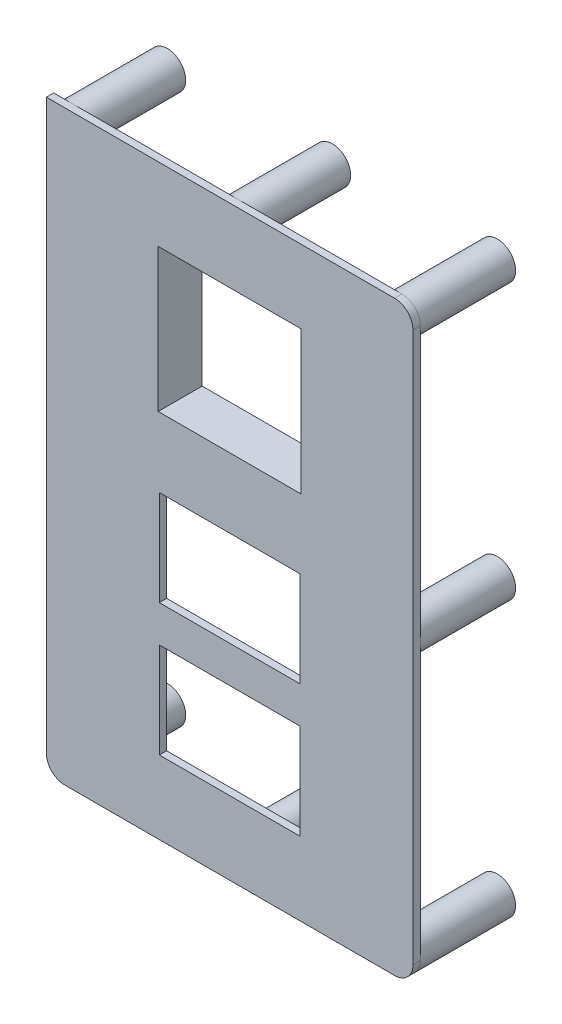
SolidWorks part; units mm, degrees
ref_plane "Front Plane" through (0, 0, 0) normal (1, 0, 0) x (0, 1, 0)
ref_plane "Top Plane" through (0, 0, 0) normal (0, 0, 1) x (0, 1, 0)
ref_plane "Right Plane" through (0, 0, 0) normal (0, 1, 0) x (-1, 0, 0)
sketch "Sketch1" plane through (0, 0, 0) normal (0, 0, 1) x (0, 1, 0)
  line L0 (-40, 0) -> (40, 0) construction
  line L1 (-40, -25) -> (40, -25)
  line L2 (-40, -25) -> (-40, 25)
  line L3 (-40, 25) -> (40, 25)
  line L4 (40, -25) -> (40, 25)
  line L5 (-40, -25) -> (40, 25) construction
  line L6 (-40, 25) -> (40, -25) construction
  line L7 (0, 25) -> (0, -25) construction
  point P0 (0, 0)
  dimension "D1" = 50
  dimension "D2" = 80
extrude "Boss-Extrude1" add sketch "Sketch1" along normal blind 1
sketch "Sketch4" plane through (0, 0, 0) normal (0, 0, -1) x (1, 0, 0)
  line L0 (0, 40) -> (0, -1) construction
  line L1 (-25, 40) -> (25, 40) construction
  line L2 (0, 0) -> (25, 0) construction
  line L3 (25, 40) -> (25, -40) construction
  line L4 (0, -1) -> (0, -40) construction
  line L5 (-9.6, 17) -> (9.6, 17)
  line L6 (-9.6, 17) -> (-9.6, 30)
  line L7 (-9.6, 30) -> (9.6, 30)
  line L8 (9.6, 17) -> (9.6, 30)
  line L9 (-9.6, 17) -> (9.6, 30) construction
  line L10 (-9.6, 30) -> (9.6, 17) construction
  line L11 (-9.6, -1) -> (9.6, -1)
  line L12 (-9.6, -1) -> (-9.6, 12)
  line L13 (-9.6, 12) -> (9.6, 12)
  line L14 (9.6, -1) -> (9.6, 12)
  line L15 (-9.6, -1) -> (9.6, 12) construction
  line L16 (-9.6, 12) -> (9.6, -1) construction
  line L17 (25, -40) -> (-25, -40) construction
  line L19 (-9.75, -30) -> (9.75, -30)
  line L20 (-9.75, -30) -> (-9.75, -10.5)
  line L21 (-9.75, -10.5) -> (9.75, -10.5)
  line L22 (9.75, -30) -> (9.75, -10.5)
  line L23 (-9.75, -30) -> (9.75, -10.5) construction
  line L24 (-9.75, -10.5) -> (9.75, -30) construction
  point P5 (0, 23.5)
  point P13 (0, 5.5)
  point P19 (0, -20.25)
  dimension "D1" = 19.2
  dimension "D2" = 13
  dimension "D3" = 19.2
  dimension "D4" = 13
  dimension "D5" = 19.5
  dimension "D6" = 19.5
  dimension "D7" = 10
  dimension "D8" = 10
  dimension "D9" = 5
extrude "Cut-Extrude1" cut sketch "Sketch4" against normal blind 1
sketch "Sketch5" plane through (0, 0, 0) normal (0, 0, -1) x (1, 0, 0)
  line L0 (0, 40) -> (0, -40) construction
  line L1 (25, 0) -> (-25, 0) construction
  line L2 (22.5, 37.5) -> (-22.5, 37.5) construction
  line L3 (-22.5, 37.5) -> (-22.5, -37.5) construction
  line L4 (-25, -40) -> (25, -40)
  line L5 (25, -40) -> (25, 40)
  line L6 (25, 40) -> (-25, 40)
  line L7 (-25, 40) -> (-25, -40)
  line L8 (-25, -40) -> (25, -40) construction
  line L9 (25, -40) -> (25, 40) construction
  line L10 (25, 40) -> (-25, 40) construction
  line L11 (-25, 40) -> (-25, -40) construction
  line L12 (-22.5, -37.5) -> (22.5, -37.5) construction
  line L13 (22.5, -37.5) -> (22.5, 37.5) construction
  circle A0 centre (0, 37.5) radius 2.5
  circle A1 centre (-22.5, 37.5) radius 2.5
  circle A2 centre (22.5, 37.5) radius 2.5
  circle A3 centre (-22.5, 0) radius 2.5
  circle A4 centre (22.5, 0) radius 2.5
  circle A5 centre (22.5, -37.5) radius 2.5
  circle A6 centre (-22.5, -37.5) radius 2.5
  circle A7 centre (0, -37.5) radius 2.5
  dimension "D1" = 0
  dimension "D2" = 2.5
extrude "Boss-Extrude2" add sketch "Sketch5" along normal blind 13
fillet "Fillet1" radius 2.5 3 edges at (25, 40, 0.5) (25, -40, 0.5) (-25, -40, 0.5)
sketch "Sketch6" plane through (0, 0, 0) normal (0, 0, -1) x (1, 0, 0)
  line L8 (9.75, -30) -> (9.75, -10.5) construction
  line L9 (-9.75, -30) -> (9.75, -30) construction
  line L10 (-9.75, -10.5) -> (-9.75, -30) construction
  line L11 (9.75, -10.5) -> (-9.75, -10.5) construction
  line L12 (9.75, -30) -> (9.75, -10.5)
  line L13 (-9.75, -30) -> (9.75, -30)
  line L14 (-9.75, -10.5) -> (-9.75, -30)
  line L15 (9.75, -10.5) -> (-9.75, -10.5)
  line L16 (-10.75, -9.5) -> (-10.75, -31)
  line L17 (-10.75, -31) -> (10.75, -31)
  line L18 (10.75, -31) -> (10.75, -9.5)
  line L19 (10.75, -9.5) -> (-10.75, -9.5)
  dimension "D1" = 1
extrude "Boss-Extrude3" add sketch "Sketch6" along normal blind 5
sketch "Sketch7" plane through (0, 0, -13) normal (0, 0, -1) x (1, 0, 0)
  circle A0 centre (22.5, -37.5) radius 2.5 construction
  circle A1 centre (0, -37.5) radius 2.5 construction
  circle A2 centre (-22.5, -37.5) radius 2.5 construction
  circle A3 centre (-22.5, 0) radius 2.5 construction
  circle A4 centre (22.5, 37.5) radius 2.5 construction
  circle A5 centre (0, 37.5) radius 2.5 construction
  circle A6 centre (-22.5, 37.5) radius 2.5 construction
  circle A7 centre (22.5, 0) radius 2.5 construction
  circle A8 centre (22.5, -37.5) radius 2.5 construction
  circle A9 centre (0, -37.5) radius 2.5 construction
  circle A10 centre (-22.5, -37.5) radius 2.5 construction
  circle A11 centre (-22.5, 0) radius 2.5 construction
  circle A12 centre (22.5, 37.5) radius 2.5 construction
  circle A13 centre (0, 37.5) radius 2.5 construction
  circle A14 centre (-22.5, 37.5) radius 2.5 construction
  circle A15 centre (22.5, 0) radius 2.5 construction
  circle A16 centre (-22.5, 37.5) radius 1.5
  circle A17 centre (0, 37.5) radius 1.5
  circle A18 centre (22.5, 37.5) radius 1.5
  circle A19 centre (-22.5, 0) radius 1.5
  circle A20 centre (22.5, 0) radius 1.5
  circle A21 centre (22.5, -37.5) radius 1.5
  circle A22 centre (0, -37.5) radius 1.5
  circle A23 centre (-22.5, -37.5) radius 1.5
  dimension "D1" = 1
extrude "Cut-Extrude2" cut sketch "Sketch7" against normal blind 10
